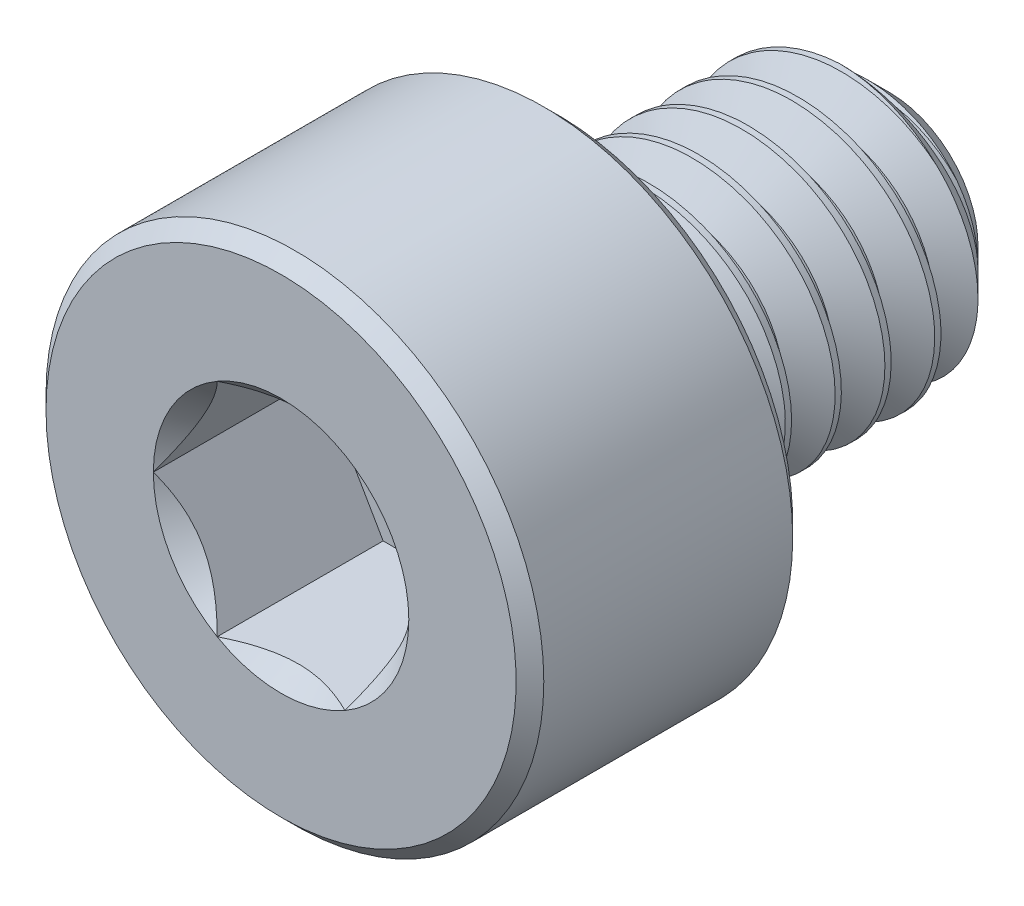
SolidWorks part; units mm, degrees
ref_plane "Front Plane" through (0, 0, 0) normal (0, 0, 1) x (1, 0, 0)
ref_plane "Top Plane" through (0, 0, 0) normal (0, 1, 0) x (1, 0, 0)
ref_plane "Right Plane" through (0, 0, 0) normal (1, 0, 0) x (0, 0, -1)
sketch "Sketch1" plane through (0, 0, 0) normal (1, 0, 0) x (0, 0, -1)
  line L0 (-2.75, 0) -> (2.75, 0) construction
  line L1 (2.75, 0) -> (2.75, 0.8) construction
  line L2 (2.75, 0.8) -> (2.3, 1.25) construction
  line L3 (2.3, 1.25) -> (1.175, 1.25) construction
  line L4 (1.175, 1.25) -> (-0.25, 1.25) construction
  line L5 (-0.25, 1.25) -> (-0.25, 2.25) construction
  line L6 (-0.25, 2.25) -> (-2.75, 2.25) construction
  line L7 (-2.75, 2.25) -> (-2.75, 0) construction
  line L8 (2.75, 0.8) -> (2.75, 1.25) construction
  line L9 (2.7219, 1.2987) -> (2.9469, 0.909) construction
  line L10 (2.9469, 0.909) -> (3.1719, 1.2987) construction
  line L11 (3.1719, 1.2987) -> (2.7219, 1.2987) construction
  line L12 (2.9469, 1.2987) -> (2.9469, 1.25) construction
  line L13 (2.9469, 0.909) -> (2.9469, 0.9577) construction
  line L14 (2.9188, 0.9577) -> (2.975, 0.9577) construction
  line L15 (2.75, 1.25) -> (3.1438, 1.25) construction
  line L16 (2.7359, 1.2744) -> (3.1578, 1.2744) construction
  line L17 (2.75, 0) -> (2.75, -1.25) construction
  line L18 (-0.375, 2.25) -> (-0.25, 2.125) construction
  line L19 (-2.625, 2.25) -> (-2.75, 2.125) construction
  point P0 (-2.75, 1)
  point P3 (1.175, 1.25)
  point P4 (0, 0)
  point P18 (0.175, 1.25)
  point P22 (2.9469, 0.9577)
  point P24 (1.175, 1.25)
  point P25 (2.9469, 1.25)
  point P28 (2.9469, 1.2744)
  point P29 (1.175, -1.25)
  point P30 (0.75, 1.25)
  point P31 (-1.5, 2.25)
  point P37 (-0.6875, 2.25)
  point P38 (-2.5625, 2.25)
  dimension "head height" = 2.5
  dimension "D1" = 45
  dimension "head dia" = 4.5
  dimension "thread dia" = 2.5
  dimension "drive size" = 2
  dimension "pitch" = 0.45
  dimension "D2" = 0.0563
  dimension "D3" = 0.45
  dimension "D4" = 1.575
  dimension "D5" = 1
  dimension "D6" = 1
  dimension "D7" = 0.125
  dimension "D8" = 0.125
  dimension "D9" = 0.125
  dimension "D10" = 0.0625
  dimension "D11" = 0.3125
  dimension "length" = 3
sketch "Sketch2" plane through (0, 0, 0) normal (1, 0, 0) x (0, 0, -1)
  line L0 (-2.75, 0) -> (-2.75, 2.125)
  line L1 (-2.625, 2.25) -> (-0.375, 2.25)
  line L2 (-0.25, 2.125) -> (-0.25, 1.25)
  line L3 (-0.25, 1.25) -> (2.3, 1.25)
  line L4 (2.3, 1.25) -> (2.75, 0.8)
  line L5 (2.75, 0.8) -> (2.75, 0)
  line L6 (-0.375, 2.25) -> (-0.25, 2.125) construction
  line L7 (2.75, 0) -> (-2.75, 0)
  line L8 (-2.625, 2.25) -> (-2.75, 2.125) construction
  line L9 (-0.375, 2.25) -> (-0.25, 2.125)
  line L10 (-2.625, 2.25) -> (-2.75, 2.125)
revolve "Revolve1" add sketch "Sketch2" angle 360 about L7
sketch "Sketch3" plane through (0, 0, 2.75) normal (0, 0, 1) x (1, 0, 0)
  line L1 (0.5774, 1) -> (-0.5774, 1)
  line L2 (-0.5774, 1) -> (-1.1547, 0)
  line L3 (-1.1547, 0) -> (-0.5774, -1)
  line L4 (-0.5774, -1) -> (0.5774, -1)
  line L5 (0.5774, -1) -> (1.1547, 0)
  line L6 (1.1547, 0) -> (0.5774, 1)
  circle A0 centre (0, 0) radius 1 construction
extrude "Cut-Extrude1" cut sketch "Sketch3" against normal offset from surface (1.5 mm away) 1 up to face at (-2.125, 0, 0.25)
sketch "Sketch4" plane through (0, 0, 2.75) normal (0, 0, 1) x (1, 0, 0)
  circle A0 centre (0, 0) radius 1.1547
extrude "Cut-Extrude2" cut sketch "Sketch4" against normal up to vertex (1.25 mm away) draft 45 up to point (0, 2.25, 1.5)
ref_plane "Plane1" through (0, 0, -1.175) normal (0, 0, 1) x (1, 0, 0)
split "Split1" bodies to split 106 resulting bodies 107 108 split by face at (-2.125, 0, 0.25)
sketch "Sketch6" plane through (0, 0, -2.75) normal (0, 0, -1) x (-1, 0, 0)
  circle A0 centre (0, 0) radius 1.25
curve "Helix/Spiral1" pitch 0.45 height 3.45 radius 1.25 centre (0, 0, -2.75) axis (0, 0, 1) start towards (0, 1, 0)
sketch "Sketch7" plane through (0, 0, 0) normal (1, 0, 0) x (0, 0, -1)
  line L0 (2.7359, 1.2744) -> (3.1578, 1.2744)
  line L1 (3.1578, 1.2744) -> (2.975, 0.9577)
  line L2 (2.975, 0.9577) -> (2.9188, 0.9577)
  line L3 (2.9188, 0.9577) -> (2.7359, 1.2744)
sweep "Cut-Sweep1" cut profiles "Sketch7" path "Helix/Spiral1" align with end faces yes
sketch "Sketch8" plane through (0, 0, 0.25) normal (0, 0, -1) x (-1, 0, 0)
  circle A0 centre (0, 0) radius 1.25
extrude "Boss-Extrude1" add sketch "Sketch8" along normal through all draft 70.5
equation "\"D2@Sketch1\"=\"pitch@Sketch1\"/8"
equation "\"D3@Sketch1\"=\"pitch@Sketch1\""
equation "\"D3@Helix/Spiral1\"=\"length@Sketch1\"+\"pitch@Sketch1\""
equation "\"D4@Helix/Spiral1\"=\"pitch@Sketch1\""
equation "\"D4@Sketch1\"=\"pitch@Sketch1\"*3.5"
equation "\"D7@Sketch1\"=\"head height@Sketch1\"*.05"
equation "\"D8@Sketch1\"=\"D7@Sketch1\""
equation "\"D9@Sketch1\"=\"D7@Sketch1\""
equation "\"D10@Sketch1\"=\"D7@Sketch1\"/2"
equation "\"D11@Sketch1\"=\"D10@Sketch1\"*5"
